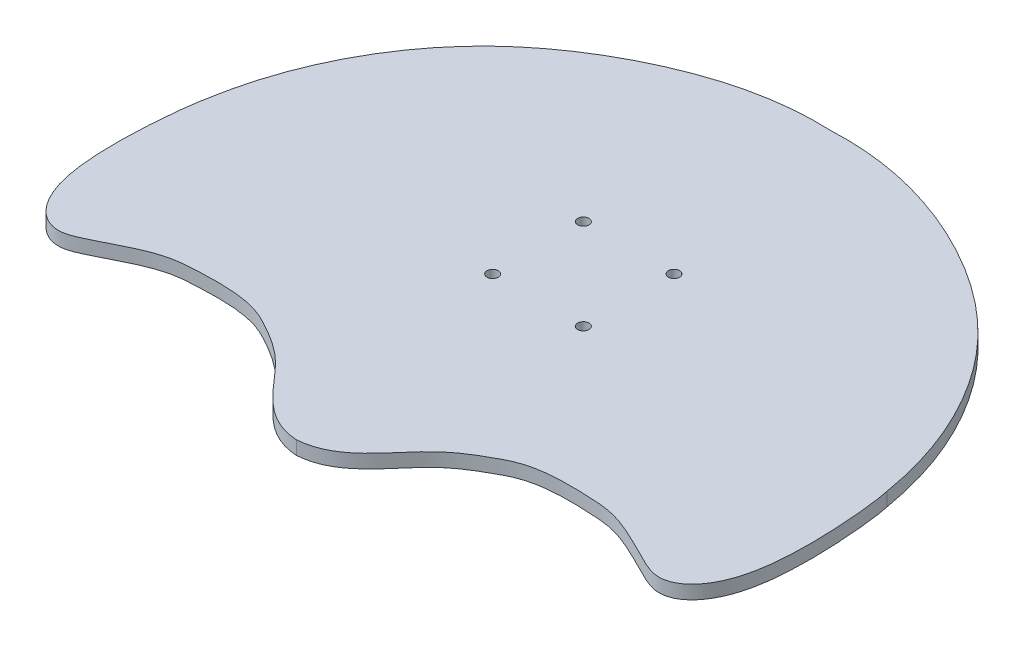
SolidWorks part; units mm, degrees
ref_plane "Front Plane" through (0, 0, 0) normal (0, 0, 1) x (1, 0, 0)
ref_plane "Top Plane" through (0, 0, 0) normal (0, 1, 0) x (1, 0, 0)
ref_plane "Right Plane" through (0, 0, 0) normal (1, 0, 0) x (0, 0, -1)
sketch "Sketch2" plane through (0, 0, 0) normal (0, 1, 0) x (1, 0, 0)
sketch "Sketch3" plane through (0, 0, 0) normal (0, 1, 0) x (1, 0, 0)
  line L0 (0, 0) -> (0, 159.1899) construction
  line L1 (0, 0) -> (0, -140.5301) construction
  line L2 (0, 0) -> (-190.5, 0) construction
  line L3 (0, 0) -> (190.5, 0) construction
  spline S0 degree 3 poles (-190.5, 0) (-184.3927, 37.537) (-157.2613, 93.9641) (-82.3875, 146.6227) (-31.3114, 160.7999) (0, 159.1899) knots 0 0 0 0 0.424401 0.65637 1 1 1 1
  spline S1 degree 3 poles (-190.5, 0) (-192.064, -4.9635) (-201.9672, -83.3146) (-174.6966, -109.29) (-151.6301, -100.568) (-131.4108, -87.7198) (-96.8436, -85.3754) (-78.6925, -86.2588) (-58.8335, -96.8794) (-37.3059, -109.9358) (-21.3496, -139.1148) (0, -140.5301) knots 0 0 0 0 0.166997 0.292321 0.319633 0.426735 0.458914 0.609242 0.64191 0.766802 1 1 1 1
  spline S2 degree 3 poles (190.5, 0) (192.064, -4.9635) (201.9672, -83.3146) (174.6966, -109.29) (151.6301, -100.568) (131.4108, -87.7198) (96.8436, -85.3754) (78.6925, -86.2588) (58.8335, -96.8794) (37.3059, -109.9358) (21.3496, -139.1148) (0, -140.5301) knots 0 0 0 0 0.166997 0.292321 0.319633 0.426735 0.458914 0.609242 0.64191 0.766802 1 1 1 1
  spline S3 degree 3 poles (190.5, 0) (184.3927, 37.537) (157.2613, 93.9641) (82.3875, 146.6227) (31.3114, 160.7999) (0, 159.1899) knots 0 0 0 0 0.424401 0.65637 1 1 1 1
  point P12 (0, 0)
  dimension "D1" = 381
  dimension "D2" = 299.72
  dimension "D3" = 159.1899
  dimension "D4" = 86.8953
  dimension "D5" = 104.4979
  dimension "D6" = 29.1616
  dimension "D7" = 92.2742
  dimension "D8" = 108.411
  dimension "D9" = 67.4883
  dimension "D10" = 43.7314
  dimension "D11" = 117.6915
  dimension "D12" = 162.2568
  dimension "D13" = 89.4522
  dimension "D14" = 140.1036
  dimension "D15" = 175.0666
  dimension "D16" = 50.2669
  dimension "D17" = 101.3666
  dimension "D18" = 138.1225
  dimension "D19" = 155.1557
  dimension "D20" = 192.0074
  dimension "D21" = 193.9268
  dimension "D23" = 76.6666
extrude "Boss-Extrude1" add sketch "Sketch3" along normal blind 7.62 from surface starting at plane "Top Plane"
sketch "Sketch5" plane through (0, 0, 0) normal (0, -1, 0) x (1, 0, 0)
  line L0 (0, 0) -> (0, -20.32) construction
  line L1 (25.4, -45.72) -> (-25.4, -45.72)
  line L2 (25.4, -45.72) -> (25.4, 5.08)
  line L3 (25.4, 5.08) -> (-25.4, 5.08)
  line L4 (-25.4, -45.72) -> (-25.4, 5.08)
  line L5 (25.4, -45.72) -> (-25.4, 5.08) construction
  line L6 (25.4, 5.08) -> (-25.4, -45.72) construction
  point P0 (0, -20.32)
  point P3 (0, -20.32)
  dimension "D1" = 20.32
  dimension "D2" = 50.8
  dimension "D3" = 50.8
hole_wizard "1/4 (0.25) Diameter Hole1" positions "Sketch6" profile "Sketch7" hole size "1/4" standard "ANSI Inch" end condition through all
sketch "Sketch6" plane through (0, 0, 0) normal (0, -1, 0) x (-1, 0, 0)
  point P0 (-25.4, 45.72)
  point P3 (25.4, 45.72)
  point P6 (25.4, -5.08)
  point P9 (-25.4, -5.08)
sketch "Sketch7" plane through (25.4, 0, -45.72) normal (1, 0, 0) x (0, 0, -1)
  line L0 (0, 0) -> (0, 7.62)
  line L1 (0, 7.62) -> (3.175, 7.62)
  line L2 (3.175, 7.62) -> (3.175, 0)
  line L5 (3.175, 0) -> (0, 0)
  line L11 (0, -6.35) -> (0, 107.95) construction
  dimension "Thru Hole Dia." = 6.35
  dimension "Thru Hole Depth" = 7.62
equation "\"Plate thickness\" = .3"
equation "\"D1@Boss-Extrude1\"=\"Plate thickness\""
equation "\"Bracket Alignment\"= .80"
equation "\"D1@Sketch5\"=\"Bracket Alignment\""
